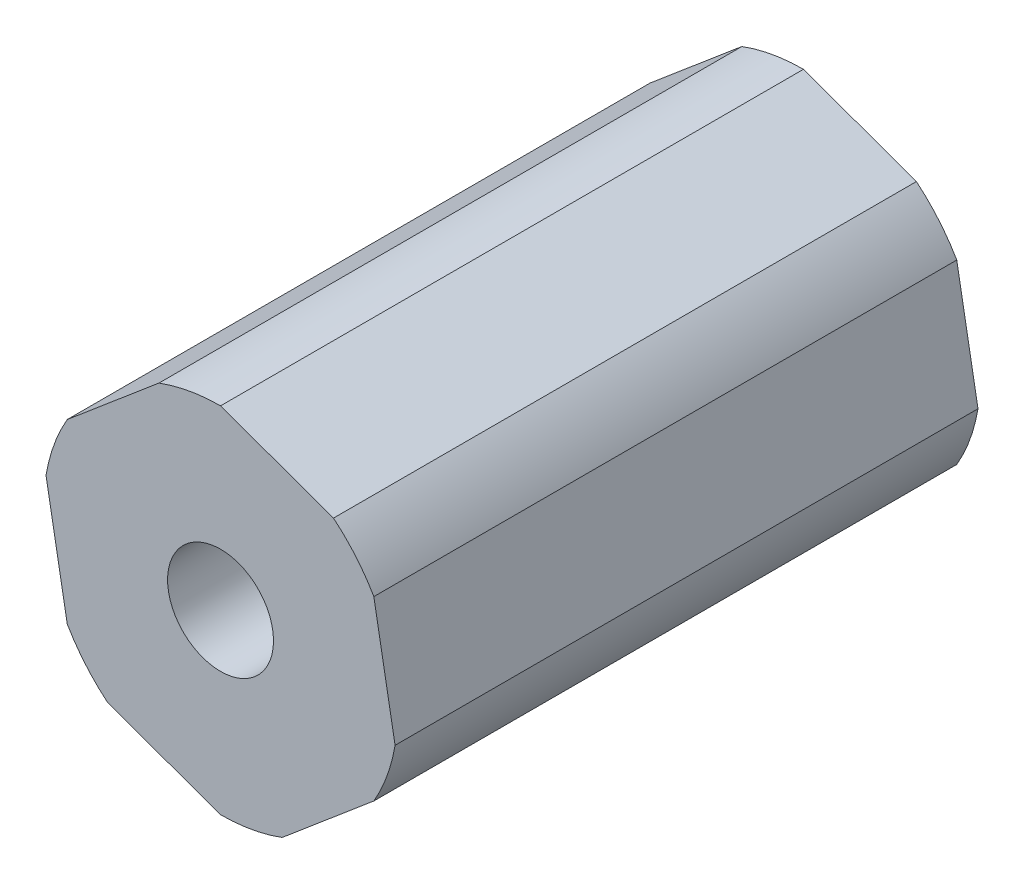
SolidWorks part; units mm, degrees
material "7075-T6 (SN)"
ref_plane "Front Plane" through (0, 0, 0) normal (0, 0, 1) x (1, 0, 0)
ref_plane "Top Plane" through (0, 0, 0) normal (0, 1, 0) x (1, 0, 0)
ref_plane "Right Plane" through (0, 0, 0) normal (1, 0, 0) x (0, 0, -1)
sketch "Sketch1" plane through (0, 0, 0) normal (0, 0, 1) x (1, 0, 0)
  line L1 (-6.6545, 1.1312) -> (-5.8457, -3.375)
  line L2 (-4.3069, -5.1974) -> (0, -6.75)
  line L3 (2.3476, -6.3286) -> (5.8457, -3.375)
  line L4 (6.6545, -1.1312) -> (5.8457, 3.375)
  line L5 (4.3069, 5.1974) -> (0, 6.75)
  line L6 (-2.3476, 6.3286) -> (-5.8457, 3.375)
  circle A0 centre (0, 0) radius 6.35 construction
  arc A1 (-5.8457, 3.375) -> (-6.6545, 1.1312) centre (0, 0) ccw
  arc A2 (-5.8457, -3.375) -> (-4.3069, -5.1974) centre (0, 0) ccw
  arc A3 (0, -6.75) -> (2.3476, -6.3286) centre (0, 0) ccw
  arc A4 (5.8457, -3.375) -> (6.6545, -1.1312) centre (0, 0) ccw
  arc A5 (5.8457, 3.375) -> (4.3069, 5.1974) centre (0, 0) ccw
  arc A6 (0, 6.75) -> (-2.3476, 6.3286) centre (0, 0) ccw
  point P6 (-6.35, 2.4899)
  point P16 (0, 0)
  dimension "D1" = 12.7
  dimension "D2" = 13.5
extrude "Boss-Extrude1" add sketch "Sketch1" along normal blind 22.225
sketch "Sketch2" plane through (0, 0, 22.225) normal (0, 0, 1) x (1, 0, 0)
  circle A0 centre (0, 0) radius 2.0193
  point P2 (0, 0)
  dimension "D1" = 4.0386
extrude "Cut-Extrude1" cut sketch "Sketch2" against normal through all
